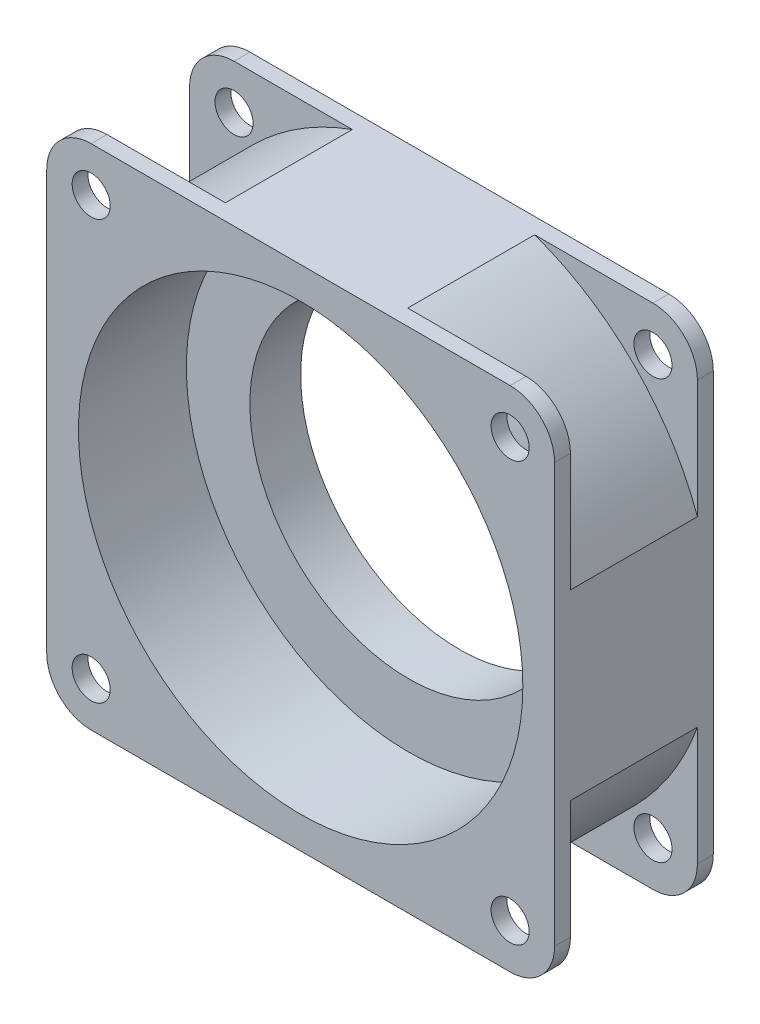
SolidWorks part; units mm, degrees
ref_plane "Front Plane" through (0, 0, 0) normal (0, 0, 1) x (1, 0, 0)
ref_plane "Top Plane" through (0, 0, 0) normal (0, 1, 0) x (1, 0, 0)
ref_plane "Right Plane" through (0, 0, 0) normal (1, 0, 0) x (0, 0, -1)
sketch "Sketch1" plane through (0, 0, 0) normal (0, 0, 1) x (1, 0, 0)
  line L0 (0, 0) -> (0, 72.0679) construction
  line L1 (-33, -40) -> (33, -40)
  line L2 (-40, -33) -> (-40, 33)
  line L3 (-33, 40) -> (33, 40)
  line L4 (40, -33) -> (40, 33)
  circle A0 centre (0, 0) radius 35
  circle A1 centre (0, 0) radius 25
  arc A2 (-33, -40) -> (-40, -33) centre (-33, -33) cw
  arc A3 (33, -40) -> (40, -33) centre (33, -33) ccw
  arc A4 (40, 33) -> (33, 40) centre (33, 33) ccw
  arc A5 (-33, 40) -> (-40, 33) centre (-33, 33) ccw
  circle A6 centre (-33, 33) radius 3
  circle A7 centre (33, 33) radius 3
  circle A8 centre (-33, -33) radius 3
  circle A9 centre (33, -33) radius 3
  point P8 (-40, 0)
  point P17 (40, -40)
  point P20 (40, 40)
  dimension "D1" = 70
  dimension "D2" = 50
  dimension "D4" = 7
  dimension "D5" = 6
  dimension "D3" = 80
extrude "Boss-Extrude1" add sketch "Sketch1" along normal mid plane 25 contours A0 L3 A5 L2 A2 L1 A3 L4 A4 A9 A8 A7 A6 | A1 A0 region at (-37.1497, -37.1497, 0) region at (-34.0101, 0, 0)
sketch "Sketch2" plane through (0, 0, 0) normal (0, 0, 1) x (1, 0, 0)
  line L0 (-40, 14.3614) -> (-40, 33)
  line L1 (-40, -33) -> (-40, 33) construction
  line L2 (-33, 40) -> (-14.3614, 40)
  line L3 (0, 0) -> (0, 10.2187) construction
  line L4 (0, 0) -> (-7.9641, 0) construction
  line L5 (33, 40) -> (14.3614, 40)
  line L6 (40, 14.3614) -> (40, 33)
  line L7 (40, -14.3614) -> (40, -33)
  line L8 (33, -40) -> (14.3614, -40)
  line L9 (-33, -40) -> (-14.3614, -40)
  line L10 (-40, -14.3614) -> (-40, -33)
  circle A0 centre (0, 0) radius 35
  circle A1 centre (0, 0) radius 42.5
  arc A2 (-33, 40) -> (-40, 33) centre (-33, 33) ccw construction
  arc A3 (-33, 40) -> (-40, 33) centre (-33, 33) ccw
  arc A4 (33, 40) -> (40, 33) centre (33, 33) cw
  arc A5 (33, -40) -> (40, -33) centre (33, -33) ccw
  arc A6 (-33, -40) -> (-40, -33) centre (-33, -33) cw
  circle A7 centre (0, 0) radius 25
  dimension "D1" = 70
  dimension "D2" = 85
extrude "Cut-Extrude2" cut sketch "Sketch2" against normal mid plane 20 contours L2 A3 L0 A1 | A4 L5 A1 L6 | L8 A5 L7 A1 | A6 L9 A1 L10 region at (-32.5306, 32.5306, 0) region at (-32.5306, -32.5306, 0) region at (32.5306, 32.5306, 0) region at (32.5306, -32.5306, 0)
extrude "Cut-Extrude3" cut sketch "Sketch2<4>" against normal blind 17 from surface contours A0 A7 region at (-34.0101, 0, 0) starting at face at (0, 0, 12.5)
sketch "Sketch2<4>" plane through (0, 0, 0) normal (0, 0, 1) x (1, 0, 0) same geometry as "Sketch2"
